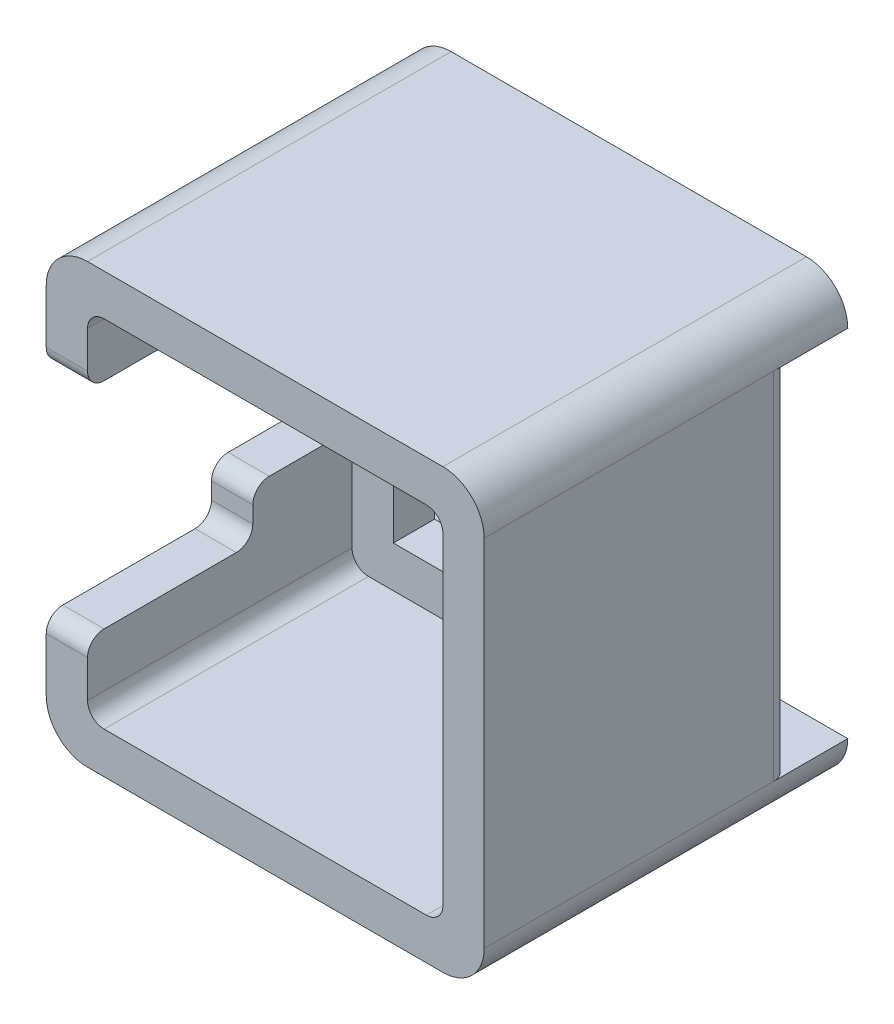
SolidWorks part; units mm, degrees
ref_plane "Alzado" through (0, 0, 0) normal (1, 0, 0) x (0, 1, 0)
ref_plane "Planta" through (0, 0, 0) normal (0, 0, 1) x (0, 1, 0)
ref_plane "Vista lateral" through (0, 0, 0) normal (0, 1, 0) x (-1, 0, 0)
sketch "Croquis1" plane through (0, 0, 0) normal (0, 0, 1) x (0, 1, 0)
  line L0 (-26.5, 0) -> (26.5, 0) construction
  line L1 (-21.5, -21.5) -> (21.5, -21.5) construction
  line L2 (-21.5, -21.5) -> (-21.5, 21.5) construction
  line L3 (-21.5, 21.5) -> (21.5, 21.5) construction
  line L4 (21.5, -21.5) -> (21.5, 21.5) construction
  line L5 (-21.5, -21.5) -> (21.5, 21.5) construction
  line L6 (-21.5, 21.5) -> (21.5, -21.5) construction
  line L7 (-21.5, 21.5) -> (-26.5, 21.5)
  line L8 (-21.5, 21.5) -> (-21.5, -21.5)
  line L9 (-21.5, -21.5) -> (-26.5, -21.5)
  line L10 (-26.5, 21.5) -> (-26.5, -21.5)
  line L11 (21.5, 21.5) -> (26.5, 21.5)
  line L12 (21.5, 21.5) -> (21.5, -21.5)
  line L13 (21.5, -21.5) -> (26.5, -21.5)
  line L14 (26.5, 21.5) -> (26.5, -21.5)
  line L15 (-21.5, 21.5) -> (-26.5, 21.5)
  line L16 (-21.5, 21.5) -> (-21.5, 26.5)
  line L17 (-21.5, 26.5) -> (-26.5, 26.5)
  line L18 (-26.5, 21.5) -> (-26.5, 26.5)
  line L19 (26.5, 21.5) -> (21.5, 21.5)
  line L20 (26.5, 21.5) -> (26.5, 26.5)
  line L21 (26.5, 26.5) -> (21.5, 26.5)
  line L22 (21.5, 21.5) -> (21.5, 26.5)
  line L23 (26.5, -26.5) -> (21.5, -26.5)
  line L24 (21.5, -21.5) -> (21.5, -26.5)
  line L25 (26.5, -21.5) -> (21.5, -21.5)
  line L26 (26.5, -21.5) -> (26.5, -26.5)
  line L27 (-21.5, -26.5) -> (-26.5, -26.5)
  line L28 (-26.5, -21.5) -> (-26.5, -26.5)
  line L29 (-21.5, -21.5) -> (-26.5, -21.5)
  line L30 (-21.5, -21.5) -> (-21.5, -26.5)
  point P0 (0, 0)
  dimension "D1" = 43
  dimension "D2" = 43
  dimension "D3" = 5
  dimension "D4" = 5
  dimension "D5" = 5
  dimension "D6" = 5
extrude "Saliente-Extruir1" add sketch "Croquis1" along normal blind 7 contours L30 L9 L28 L27 | L26 L13 L24 L23 | L8 L7 L10 L9 | L16 L15 L18 L17 | L20 L19 L22 L21 | L12 L11 L14 L13 region at (24, -24, 0) region at (24, 24, 0)
sketch "Croquis3" plane through (0, 0, 7) normal (0, 0, 1) x (1, 0, 0)
  line L1 (-26.5, -26.5) -> (-26.5, 26.5)
  line L3 (-26.5, 26.5) -> (26.5, 26.5)
  line L4 (-26.5, 26.5) -> (26.5, 26.5) construction
  line L10 (26.5, -26.5) -> (-26.5, -26.5) construction
  line L11 (16.5, 16.5) -> (-16.5, 16.5)
  line L12 (16.5, 16.5) -> (16.5, -16.5)
  line L13 (16.5, -16.5) -> (-16.5, -16.5)
  line L14 (-16.5, 16.5) -> (-16.5, -16.5)
  line L15 (16.5, 16.5) -> (-16.5, -16.5) construction
  line L16 (16.5, -16.5) -> (-16.5, 16.5) construction
  line L17 (-26.5, -26.5) -> (26.5, -26.5)
  line L20 (26.5, -26.5) -> (26.5, 26.5)
  line L22 (-26.5, -21.5) -> (-26.5, -26.5) construction
  point P0 (0, 0)
  point P3 (26.6923, 26.5)
  point P4 (0, 0)
  point P8 (-26.0112, -26.5)
  point P14 (0, 0)
  line M33 (26.5, -26.5) -> (26.5, -21.5)
  line M34 (26.5, -21.5) -> (-26.5, -21.5)
  line M35 (-26.5, -21.5) -> (-26.5, -26.5)
  line M36 (-26.5, -26.5) -> (26.5, -26.5)
  dimension "D1" = 10
  dimension "D2" = 10
  dimension "D3" = 10
extrude "Saliente-Extruir2" add sketch "Croquis3" along normal blind 5 contours L20 L3 L1 L14 L11 L12 L13 M34 | M36 M33 M34 M35
sketch "Croquis4" plane through (0, 0, 12) normal (0, 0, 1) x (1, 0, 0)
  line L1 (-26.5, -26.5) -> (26.5, -26.5)
  line L2 (-26.5, -26.5) -> (-26.5, 26.5)
  line L3 (-26.5, 26.5) -> (26.5, 26.5)
  line L4 (26.5, -26.5) -> (26.5, 26.5)
  line L5 (-21.5, -21.5) -> (21.5, -21.5)
  line L6 (-21.5, -21.5) -> (-21.5, 21.5)
  line L7 (-21.5, 21.5) -> (21.5, 21.5)
  line L8 (21.5, -21.5) -> (21.5, 21.5)
  line L9 (-21.5, -21.5) -> (21.5, 21.5) construction
  line L10 (-21.5, 21.5) -> (21.5, -21.5) construction
  point P6 (0, 0)
  dimension "D1" = 5
  dimension "D2" = 5
extrude "Saliente-Extruir3" add sketch "Croquis4" along normal blind 32
fillet "Redondeo1" radius 2 4 edges at (21.5, -21.5, 28) (21.5, 21.5, 28) (-21.5, 21.5, 28) (-21.5, -21.5, 28)
fillet "Redondeo2" radius 5 4 edges at (-26.5, 26.5, 22) (26.5, 26.5, 22) (26.5, -26.5, 22) (-26.5, -26.5, 22)
sketch "Croquis5" plane through (0, 0, 44) normal (0, 0, 1) x (1, 0, 0)
  line L0 (-26.5, 21.5) -> (-26.5, -21.5) construction
  line L1 (-26.5, -7) -> (-21.5, -7)
  line L2 (-26.5, -7) -> (-26.5, 7)
  line L3 (-26.5, 7) -> (-21.5, 7)
  line L4 (-21.5, -7) -> (-21.5, 7)
  line L5 (-21.5, 19.5) -> (-21.5, -19.5) construction
  point P8 (-21.5, 0)
  dimension "D1" = 14
extrude "Cortar-Extruir1" cut sketch "Croquis5" against normal up to surface (32 mm away) up to face at (0, 0, 12)
sketch "Croquis6" plane through (0, 0, 44) normal (0, 0, 1) x (1, 0, 0)
  line L1 (-26.5, 7) -> (-21.5, 7)
  line L2 (-26.5, 7) -> (-26.5, 13)
  line L3 (-26.5, 13) -> (-21.5, 13)
  line L4 (-21.5, 7) -> (-21.5, 13)
  line L5 (-21.5, -7) -> (-21.5, -19.5) construction
  line L6 (-26.5, -7) -> (-21.5, -7)
  line L7 (-26.5, -7) -> (-26.5, -13)
  line L8 (-26.5, -13) -> (-21.5, -13)
  line L9 (-21.5, -7) -> (-21.5, -13)
  line L10 (-26.5, 21.5) -> (-26.5, 7) construction
  dimension "D1" = 6
  dimension "D2" = 6
  dimension "D3" = 5
extrude "Cortar-Extruir2" cut sketch "Croquis6" against normal blind 20 contours L7 L6 L9 L8 | L2 L1 L4 L3
fillet "Redondeo3" radius 2 10 edges at (26.5, 0, 7) (-26.5, 0, 7) (-24, -7, 12) (-24, 7, 12) (-24, -13, 44) (-24, -13, 24) (-24, -7, 24) (-24, 7, 24) (-24, 13, 24) (-24, 13, 44)
sketch "Croquis7" plane through (0, 0, 0) normal (0, 0, 1) x (0, 1, 0)
  line L5 (0, 0) -> (-21.5, 0) construction
  line L6 (-21.5, 19.5) -> (-21.5, -19.5) construction
  line L7 (0, 16.5) -> (0, -16.5) construction
  line L8 (16.5, 16.5) -> (-16.5, 16.5) construction
  line L9 (16.5, -16.5) -> (-16.5, -16.5) construction
  line L10 (-21.5, -7.5) -> (-21.5, 7.5)
  line L11 (-21.5, 7.5) -> (-9.3437, 3.8292)
  line L12 (-21.5, -7.5) -> (-9.3437, -3.8292)
  circle A0 centre (-10.5, 0) radius 1.75
  circle A1 centre (-10.5, 0) radius 4
  point P14 (-21.5, 0)
  dimension "D1" = 3.5
  dimension "D4" = 2.25
  dimension "D2" = 11
  dimension "D3" = 15
extrude "Saliente-Extruir4" add sketch "Croquis7" along normal blind 3 contours A1 L11 L10 L12 | A1 A0 region at (0, -17.5632, 0) region at (0, -14.3869, 0)
fillet "Redondeo4" radius 3 2 edges at (-7.5, -21.5, 1.5) (7.5, -21.5, 1.5)
mirror "Simetría5" about plane through (0, 0, 0) normal (0, 1, 0) of "Saliente-Extruir4"
fillet "Redondeo7" radius 3 2 edges at (7.5, 21.5, 1.5) (-7.5, 21.5, 1.5)
